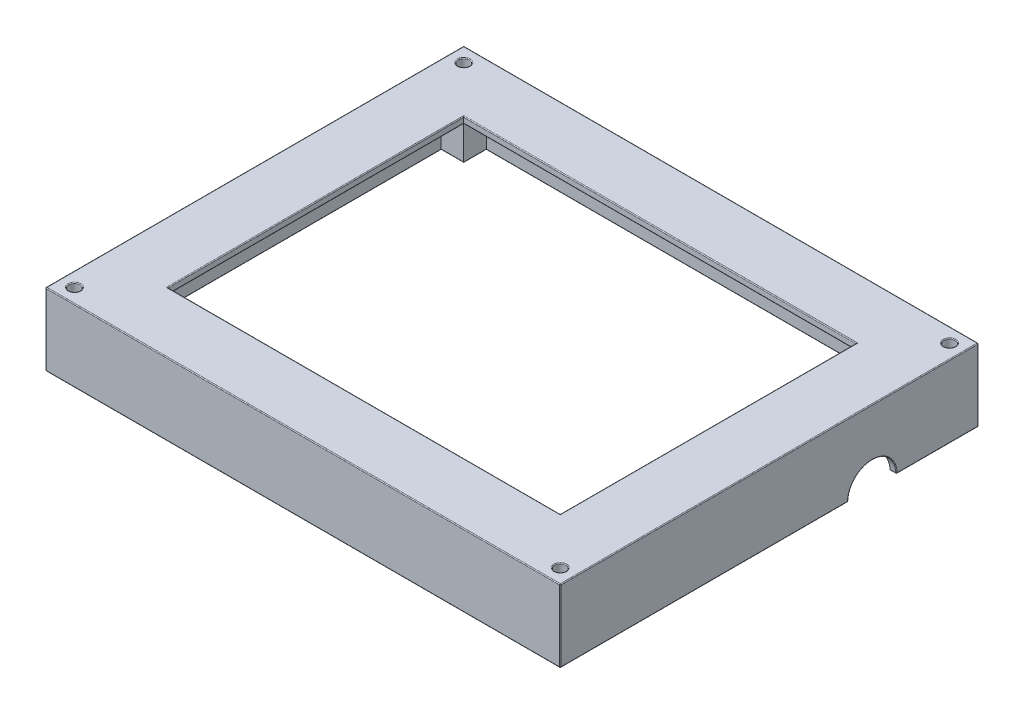
SolidWorks part; units mm, degrees
note: The reader was unsure of these and kept them because the rebuilt part matched: shared geometry of "Sketch1<3>", "Sketch1<5>".
ref_plane "Front Plane" through (0, 0, 0) normal (0, 0, 1) x (1, 0, 0)
ref_plane "Top Plane" through (0, 0, 0) normal (0, 1, 0) x (1, 0, 0)
ref_plane "Right Plane" through (0, 0, 0) normal (1, 0, 0) x (0, 0, -1)
sketch "Sketch1" plane through (0, 0, 0) normal (0, 1, 0) x (1, 0, 0)
  line L0 (0, 121) -> (9, 121)
  line L1 (2, 121) -> (2, 9)
  line L2 (9, 2) -> (151, 2)
  line L3 (158, 9) -> (158, 121)
  line L4 (19, 111) -> (141, 111)
  line L5 (7.125, 123.9845) -> (7.125, 127.0155)
  line L6 (7.125, 127.0155) -> (4.5, 128.5311)
  line L7 (0, 130) -> (160, 130)
  line L8 (0, 130) -> (0, 0)
  line L9 (0, 0) -> (160, 0)
  line L10 (160, 130) -> (160, 0)
  line L11 (9, 121) -> (9, 130)
  line L12 (0, 9) -> (9, 9)
  line L13 (9, 9) -> (9, 0)
  line L14 (151, 0) -> (151, 9)
  line L15 (151, 9) -> (160, 9)
  line L16 (160, 121) -> (151, 121)
  line L17 (151, 121) -> (151, 130)
  line L18 (4.5, 128.5311) -> (1.875, 127.0155)
  line L19 (9, 121) -> (0, 130) construction
  line L20 (151, 121) -> (160, 130) construction
  line L21 (9, 9) -> (0, 0) construction
  line L22 (151, 9) -> (160, 0) construction
  line L23 (1.875, 127.0155) -> (1.875, 123.9845)
  line L24 (1.875, 123.9845) -> (4.5, 122.4689)
  line L25 (4.5, 122.4689) -> (7.125, 123.9845)
  line L34 (158.125, 123.9845) -> (158.125, 127.0155)
  line L35 (0, 0) -> (160, 0) construction
  line L36 (0, 0) -> (0, 50) construction
  line L37 (158.125, 127.0155) -> (155.5, 128.5311)
  line L38 (160, 0) -> (160, 50) construction
  line L39 (151, 128) -> (9, 128)
  line L40 (155.5, 128.5311) -> (152.875, 127.0155)
  line L41 (152.875, 127.0155) -> (152.875, 123.9845)
  line L42 (152.875, 123.9845) -> (155.5, 122.4689)
  line L43 (155.5, 122.4689) -> (158.125, 123.9845)
  line L44 (158.125, 2.9845) -> (158.125, 6.0155)
  line L45 (158.125, 6.0155) -> (155.5, 7.5311)
  line L46 (155.5, 7.5311) -> (152.875, 6.0155)
  line L47 (152.875, 6.0155) -> (152.875, 2.9845)
  line L48 (152.875, 2.9845) -> (155.5, 1.4689)
  line L49 (155.5, 1.4689) -> (158.125, 2.9845)
  line L50 (7.125, 2.9845) -> (7.125, 6.0155)
  line L51 (7.125, 6.0155) -> (4.5, 7.5311)
  line L52 (4.5, 7.5311) -> (1.875, 6.0155)
  line L53 (1.875, 6.0155) -> (1.875, 2.9845)
  line L54 (1.875, 2.9845) -> (4.5, 1.4689)
  line L55 (4.5, 1.4689) -> (7.125, 2.9845)
  line L56 (9, 121) -> (151, 121) construction
  line L57 (9, 121) -> (9, 9) construction
  line L58 (9, 9) -> (151, 9) construction
  line L59 (151, 121) -> (151, 9) construction
  line L60 (141, 111) -> (141, 19)
  line L61 (19, 19) -> (141, 19)
  line L62 (19, 111) -> (19, 19)
  circle A0 centre (4.5, 125.5) radius 1.75
  circle A1 centre (155.5, 125.5) radius 1.75
  circle A2 centre (155.5, 4.5) radius 1.75
  circle A3 centre (4.5, 4.5) radius 1.75
  circle A4 centre (4.5, 125.5) radius 2.625 construction
  circle A5 centre (155.5, 125.5) radius 2.625 construction
  circle A6 centre (155.5, 4.5) radius 2.625 construction
  circle A7 centre (4.5, 4.5) radius 2.625 construction
  point P67 (7.5311, 125.5)
  point P68 (0, 0)
  dimension "D5" = 3.5
  dimension "D8" = 5.25
  dimension "D2" = 130
  dimension "D3" = 9
  dimension "D4" = 2
  dimension "D6" = 2
  dimension "D7" = 2
  dimension "D9" = 10
  dimension "D10" = 160
  dimension "D11" = 50
  dimension "D13" = 2
extrude "Boss-Extrude1" add sketch "Sketch1" against normal blind 2 contours L0 L11 L7 L8 A0 | L8 L12 L1 L0 | L39 L17 L7 L11 | L13 L12 L8 L9 A3 | L9 L14 L2 L13 | L10 L16 L3 L15 | L15 L14 L9 L10 A2 | L17 L16 L10 L7 A1 | L17 L39 L11 L0 L1 L12 L13 L2 L14 L15 L3 L16 L62 L4 L60 L61
extrude "Boss-Extrude3" add sketch "Sketch1<3>" against normal blind 22.5 contours L10 L16 L3 L15 | L17 L16 L10 L7 L43 L42 L41 L40 L37 L34 | L39 L17 L7 L11 | L0 L11 L7 L8 L25 L24 L23 L18 L6 L5 | L8 L12 L1 L0 | L15 L14 L9 L10 L49 L48 L47 L46 L45 L44 | L9 L14 L2 L13 | L13 L12 L8 L9 L55 L54 L53 L52 L51 L50
sketch "Sketch1<3>" plane through (0, 0, 0) normal (0, 1, 0) x (1, 0, 0) same geometry as "Sketch1"
extrude "Boss-Extrude5" add sketch "Sketch1<5>" against normal blind 14.5 contours L24 L25 L5 L6 L18 L23 A0 | L54 L55 L50 L51 L52 L53 A3 | L48 L49 L44 L45 L46 L47 A2 | L42 L43 L34 L37 L40 L41 A1
sketch "Sketch1<5>" plane through (0, 0, 0) normal (0, 1, 0) x (1, 0, 0) same geometry as "Sketch1"
sketch "Sketch3" plane through (160, 0, 0) normal (1, 0, 0) x (0, 0, -1)
  line L0 (97, 0) -> (97, -22.5) construction
  line L3 (97, 0) -> (130, 0) construction
  line L4 (130, -22.5) -> (0, -22.5) construction
  circle A1 centre (97, -22.5) radius 7.5
  dimension "D2" = 15
  dimension "D1" = 33
extrude "Cut-Extrude1" cut sketch "Sketch3" against normal blind 4.5
fillet "Fillet1" radius 0.25 77 edges at (0, -22.5, -65) (80, -22.5, 0) (2, -2, -65) (5.5, -2, -9) (9, -2, -5.5) (80, -2, -2) (151, -2, -5.5) (154.5, -2, -9) (158, -2, -65) (154.5, -2, -121) (151, -2, -124.5) (80, -2, -128) (9, -22.5, -124.5) (5.5, -22.5, -121) (9, -2, -124.5) (5.5, -2, -121) (2, -22.5, -65) (5.5, -22.5, -9) (9, -22.5, -5.5) (80, -22.5, -2) (151, -22.5, -5.5) (154.5, -22.5, -9) (158, -22.5, -49.25) (154.5, -22.5, -121) (151, -22.5, -124.5) (80, -22.5, -128) (160, -22.5, -117.25) (80, -22.5, -130) (156.8125, -22.5, -2.2267) (158.125, -22.5, -4.5) (156.8125, -22.5, -6.7733) (154.1875, -22.5, -6.7733) (152.875, -22.5, -4.5) (154.1875, -22.5, -2.2267) (156.8125, -22.5, -123.2267) (158.125, -22.5, -125.5) (156.8125, -22.5, -127.7733) (154.1875, -22.5, -127.7733) (152.875, -22.5, -125.5) (154.1875, -22.5, -123.2267) (5.8125, -22.5, -2.2267) (7.125, -22.5, -4.5) (5.8125, -22.5, -6.7733) (3.1875, -22.5, -6.7733) (1.875, -22.5, -4.5) (3.1875, -22.5, -2.2267) (5.8125, -22.5, -123.2267) (7.125, -22.5, -125.5) (5.8125, -22.5, -127.7733) (3.1875, -22.5, -127.7733) (1.875, -22.5, -125.5) (3.1875, -22.5, -123.2267) (155.5, 0, -123.75) (155.5, 0, -2.75) (4.5, 0, -2.75) (4.5, 0, -123.75) (158, -22.5, -112.75) (160, -22.5, -44.75) (159, -22.5, -104.5) (159, -22.5, -89.5) (160, -15, -97) (80, 0, -19) (141, 0, -65) (80, 0, -111) (19, 0, -65) (80, 0, -130) (160, 0, -65) (80, 0, 0) (0, 0, -65) (0, -11.25, -130) (160, -11.25, -130) (160, -11.25, 0) (0, -11.25, 0) (19, -2, -65) (80, -2, -111) (141, -2, -65) (80, -2, -19)
